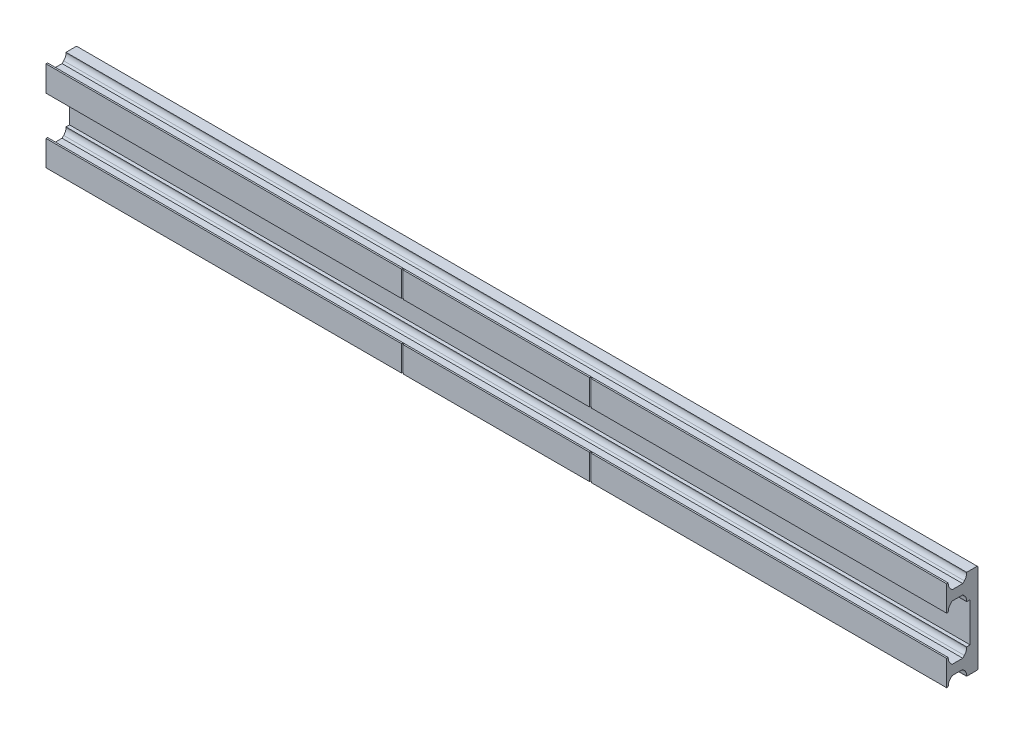
SolidWorks part; units mm, degrees
ref_plane "Front" through (0, 0, 0) normal (0, 0, 1) x (1, 0, 0)
ref_plane "Top" through (0, 0, 0) normal (0, 1, 0) x (1, 0, 0)
ref_plane "Right" through (0, 0, 0) normal (1, 0, 0) x (0, 0, -1)
sketch "Sketch1" plane through (0, 0, 0) normal (0, 0, 1) x (1, 0, 0)
  line L0 (115, -4.5) -> (115, 4.5) construction
  line L1 (-115, 11.5) -> (115, 11.5)
  line L2 (-115, 11.5) -> (-115, -11.5)
  line L3 (-115, -11.5) -> (115, -11.5)
  line L4 (115, 11.5) -> (115, -11.5)
  line L5 (-115, 11.5) -> (115, -11.5) construction
  line L6 (-115, -11.5) -> (115, 11.5) construction
  point P0 (0, 0)
  dimension "D1" = 7
extrude "Boss-Extrude1" add sketch "Sketch1" against normal blind 2
sketch "Sketch2" plane through (0, 0, 0) normal (0, 0, 1) x (1, 0, 0)
  line L0 (115, 11.5) -> (115, -11.5) construction
  line L1 (-115, 11.5) -> (115, 11.5)
  line L2 (-115, 11.5) -> (-115, 5)
  line L3 (-115, 5) -> (115, 5)
  line L4 (115, 11.5) -> (115, 5)
  line L5 (-115, -11.5) -> (-115, 11.5) construction
  line L6 (-115, -11.5) -> (115, -11.5)
  line L7 (-115, -11.5) -> (-115, -5)
  line L8 (-115, -5) -> (115, -5)
  line L9 (115, -11.5) -> (115, -5)
  line L11 (-115, 4.5) -> (115, 4.5) construction
  dimension "D1" = 0.5
extrude "Boss-Extrude2" add sketch "Sketch2" along normal offset from surface (6 mm away) 1
ref_plane "Center of Slots" through (0, 8.25, 0) normal (0, -1, 0) x (-1, 0, 0)
sketch "Sketch5" plane through (0, 0, 0) normal (1, 0, 0) x (0, 0, -1)
  line L16 (-1.9, 7) -> (-4.6, 7)
  line L17 (-1.9, 7) -> (-4.6, 7)
  line L18 (-4.6, 7) -> (-5.0142, 6.5858)
  line L19 (-4.6, 7) -> (-5.0142, 6.5858)
  line L20 (-5.6, 5.1716) -> (-5.6, 4.3284)
  line L21 (-5.6, 5.1716) -> (-5.6, 4.3284)
  line L22 (-5.0142, 2.9142) -> (-4.6, 2.5)
  line L23 (-5.0142, 2.9142) -> (-4.6, 2.5)
  line L24 (-4.6, 2.5) -> (-1.9, 2.5)
  line L25 (-4.6, 2.5) -> (-1.9, 2.5)
  line L26 (-1.9, 2.5) -> (-1.4858, 2.9142)
  line L27 (-1.9, 2.5) -> (-1.4858, 2.9142)
  line L28 (-0.9, 4.3284) -> (-0.9, 5.1716)
  line L29 (-0.9, 4.3284) -> (-0.9, 5.1716)
  line L30 (-1.4858, 6.5858) -> (-1.9, 7)
  line L31 (-1.4858, 6.5858) -> (-1.9, 7)
  arc A12 (-5.0142, 6.5858) -> (-5.6, 5.1716) centre (-3.6, 5.1716) ccw
  arc A13 (-5.0142, 6.5858) -> (-5.6, 5.1716) centre (-3.6, 5.1716) ccw
  arc A14 (-5.6, 4.3284) -> (-5.0142, 2.9142) centre (-3.6, 4.3284) ccw
  arc A15 (-5.6, 4.3284) -> (-5.0142, 2.9142) centre (-3.6, 4.3284) ccw
  arc A16 (-1.4858, 2.9142) -> (-0.9, 4.3284) centre (-2.9, 4.3284) ccw
  arc A17 (-1.4858, 2.9142) -> (-0.9, 4.3284) centre (-2.9, 4.3284) ccw
  arc A18 (-0.9, 5.1716) -> (-1.4858, 6.5858) centre (-2.9, 5.1716) ccw
  arc A19 (-0.9, 5.1716) -> (-1.4858, 6.5858) centre (-2.9, 5.1716) ccw
  dimension "D1" = 0
extrude "Middle Slot" cut sketch "Sketch5" against normal through all both and the other way through all
mirror "Middle Slots" about plane through (0, 0, 0) normal (0, 1, 0) of "Middle Slot"
sketch "Sketch7" plane through (0, 0, 0) normal (1, 0, 0) x (0, 0, -1)
  line L8 (-1.875, 13.975) -> (-4.625, 13.975)
  line L9 (-4.625, 13.975) -> (-5.0142, 13.5858)
  line L10 (-5.6, 12.1716) -> (-5.6, 11.3284)
  line L11 (-5.0142, 9.9142) -> (-4.6, 9.5)
  line L12 (-4.6, 9.5) -> (-1.9, 9.5)
  line L13 (-1.9, 9.5) -> (-1.4858, 9.9142)
  line L14 (-0.9, 11.3284) -> (-0.9, 12.1716)
  line L15 (-1.4858, 13.5858) -> (-1.875, 13.975)
  line L16 (-1.875, 13.975) -> (-4.625, 13.975)
  line L17 (-4.625, 13.975) -> (-5.0142, 13.5858)
  line L18 (-5.6, 12.1716) -> (-5.6, 11.3284)
  line L19 (-5.0142, 9.9142) -> (-4.6, 9.5)
  line L20 (-4.6, 9.5) -> (-1.9, 9.5)
  line L21 (-1.9, 9.5) -> (-1.4858, 9.9142)
  line L22 (-0.9, 11.3284) -> (-0.9, 12.1716)
  line L23 (-1.4858, 13.5858) -> (-1.875, 13.975)
  arc A4 (-5.0142, 13.5858) -> (-5.6, 12.1716) centre (-3.6, 12.1716) ccw
  arc A5 (-5.6, 11.3284) -> (-5.0142, 9.9142) centre (-3.6, 11.3284) ccw
  arc A6 (-1.4858, 9.9142) -> (-0.9, 11.3284) centre (-2.9, 11.3284) ccw
  arc A7 (-0.9, 12.1716) -> (-1.4858, 13.5858) centre (-2.9, 12.1716) ccw
  arc A8 (-5.0142, 13.5858) -> (-5.6, 12.1716) centre (-3.6, 12.1716) ccw
  arc A9 (-5.6, 11.3284) -> (-5.0142, 9.9142) centre (-3.6, 11.3284) ccw
  arc A10 (-1.4858, 9.9142) -> (-0.9, 11.3284) centre (-2.9, 11.3284) ccw
  arc A11 (-0.9, 12.1716) -> (-1.4858, 13.5858) centre (-2.9, 12.1716) ccw
  dimension "D1" = 0
extrude "Top Slot" cut sketch "Sketch7" against normal through all both and the other way through all
mirror "Top Slots" about plane through (0, 0, 0) normal (0, 1, 0) of "Top Slot"
chamfer "Deburs" distance 0.2 angle 45 2 edges at (0, -11.5, -2) (0, 11.5, -2)
sketch "Sketch8" plane through (0, 0, 6) normal (0, 0, -1) x (-1, 0, 0)
  line L0 (-24, -14.5) -> (-24, 14.5)
  line L1 (-115, 11.5) -> (-115, -11.5) construction
  line L2 (115, 11.5) -> (-115, 11.5) construction
  line L3 (115, -11.5) -> (-115, -11.5) construction
  dimension "D1" = 91
  dimension "D2" = 3
  dimension "D3" = 3
extrude "Fill Marker" cut sketch "Sketch8" along normal blind 0.2 thin thin type mid plane wall 0.5
mirror "Fill Markers" about plane through (0, 0, 0) normal (1, 0, 0) of "Fill Marker"
